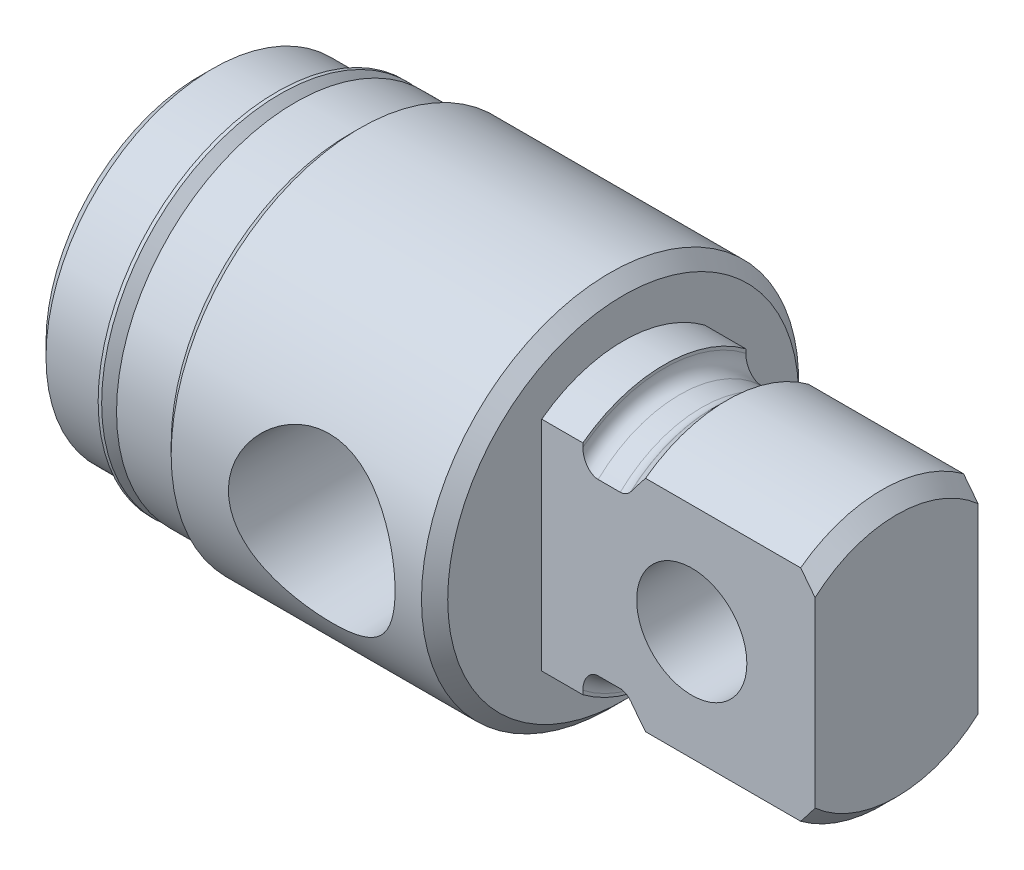
SolidWorks part; units mm, degrees
material "AISI 304"
ref_plane "Front Plane" through (0, 0, 0) normal (0, 0, 1) x (1, 0, 0)
ref_plane "Top Plane" through (0, 0, 0) normal (0, 1, 0) x (1, 0, 0)
ref_plane "Right Plane" through (0, 0, 0) normal (1, 0, 0) x (0, 0, -1)
ref_plane "Plane1" through (40.4876, 0, 0) normal (1, 0, 0) x (0, 0, -1)
sketch "Sketch1" plane through (0, 0, 0) normal (0, 0, 1) x (1, 0, 0)
  line L0 (0, 0) -> (0, 8.9091)
  line L1 (0, 8.9091) -> (0.762, 9.671)
  line L2 (0.762, 9.671) -> (4.0386, 9.671)
  line L3 (4.0386, 9.671) -> (4.8006, 8.9091)
  line L4 (4.8006, 8.9091) -> (5.5626, 8.9091)
  line L5 (5.5626, 8.9091) -> (5.5626, 10.3759)
  line L6 (5.5626, 10.3759) -> (8.7363, 10.3759)
  line L7 (8.7363, 10.3759) -> (9.3142, 10.9537)
  line L8 (9.3142, 10.9537) -> (23.8506, 10.9537)
  line L9 (23.8506, 10.9537) -> (24.6126, 10.1918)
  line L10 (24.6126, 10.1918) -> (24.6126, 0)
  line L11 (24.6126, 0) -> (0, 0)
  line L12 (24.6126, 0) -> (0, 0) construction
revolve "Revolve1" add sketch "Sketch1" angle 360 about L12 reverse direction yes
sketch "Sketch2" plane through (0, 0, 0) normal (0, 0, 1) x (1, 0, 0)
  line L0 (24.6126, 0) -> (24.6126, 7.9057)
  line L1 (24.6126, 7.9057) -> (27.0002, 7.9057)
  line L2 (27.0002, 7.9057) -> (27.0002, 7.7279)
  line L3 (27.8892, 6.8389) -> (29.1719, 6.8389)
  line L4 (29.7706, 7.0708) -> (29.8005, 7.098)
  line L5 (29.8005, 7.098) -> (30.64, 7.9375)
  line L6 (30.64, 7.9375) -> (39.6481, 7.9375)
  line L7 (39.6481, 7.9375) -> (40.4876, 7.098)
  line L8 (40.4876, 7.098) -> (40.4876, 0)
  line L9 (40.4876, 0) -> (24.6126, 0)
  line L10 (40.4876, 0) -> (24.6126, 0) construction
  arc A0 (27.0002, 7.7279) -> (27.8892, 6.8389) centre (27.8892, 7.7279) ccw
  arc A1 (29.1719, 6.8389) -> (29.7706, 7.0708) centre (29.1719, 7.7279) ccw
revolve "Revolve2" add sketch "Sketch2" angle 360 about L10 reverse direction yes
cosmetic thread "Cosmetic Thread1" parameters "D1"=10.6871, "D2"=14.1961
sketch "Sketch3" plane through (40.4876, 0, 0) normal (1, 0, 0) x (0, 0, -1)
  line L0 (-21.9075, -43.815) -> (21.9075, -43.815)
  line L1 (21.9075, -43.815) -> (21.9075, 43.815)
  line L2 (21.9075, 43.815) -> (-21.9075, 43.815)
  line L3 (-21.9075, 43.815) -> (-21.9075, -43.815)
  line L4 (-4.7307, -21.9075) -> (4.7307, -21.9075)
  line L5 (4.7307, -21.9075) -> (4.7307, 21.9075)
  line L6 (4.7307, 21.9075) -> (-4.7307, 21.9075)
  line L7 (-4.7307, 21.9075) -> (-4.7307, -21.9075)
extrude "Cut-Extrude1" cut sketch "Sketch3" against normal blind 15.875
ref_plane "Plane2" through (24.6126, 0, 0) normal (1, 0, 0) x (0, 0, -1)
hole_wizard "Hole1" positions "Sketch5" profile "Sketch4" legacy
sketch "Sketch5" plane through (0, 0, 0) normal (-1, 0, 0) x (0, 0, 1)
  point P0 (0, 0)
sketch "Sketch4" plane through (0, 0, 0) normal (0, 1, 0) x (0, 0, 1)
  line L0 (0, 0) -> (0, 25.8691)
  line L1 (0, 25.8691) -> (3.9624, 23.5814)
  line L2 (3.9624, 23.5814) -> (3.9624, 0)
  line L4 (3.9624, 0) -> (0, 0)
  line L6 (0, 25.8691) -> (-3.9624, 23.5814) construction
  line L7 (0, -4.2442) -> (0, 117.3081) construction
  dimension "Diameter" = 7.9248
  dimension "Depth" = 23.5814
  dimension "Drill Angle" = 120
ref_plane "Plane3" through (0, 0, 0) normal (0, 0.9998, 0.0175) x (1, 0, 0)
sketch "Sketch6" plane through (0, 0, 0) normal (0, 0.9998, 0.0175) x (1, 0, 0)
  line L0 (17.4752, 0) -> (22.0752, 0)
  line L1 (22.0752, 0) -> (22.0752, -3.2829)
  line L2 (22.0752, -3.2829) -> (22.3147, -10.9537)
  line L3 (22.3147, -10.9537) -> (17.4752, -10.9537)
  line L4 (17.4752, -10.9537) -> (17.4752, 0)
  line L5 (17.4752, -10.9537) -> (17.4752, 0) construction
revolve "Cut-Revolve1" cut sketch "Sketch6" angle 360 about L5 reverse direction yes
ref_plane "Plane4" through (17.4752, 0, 0) normal (1, 0, 0) x (0, 0, -1)
ref_plane "Plane5" through (4.8006, 0, 0) normal (1, 0, 0) x (0, 0, -1)
sketch "Sketch7" plane through (0, 0, 0) normal (0, 0, 1) x (1, 0, 0)
  line L0 (4.4955, 10.2917) -> (5.4401, 9.3472)
  line L1 (5.4401, 9.1676) -> (5.1816, 8.9091)
  line L2 (5.1816, 8.9091) -> (4.8006, 8.9091)
  line L3 (4.8006, 8.9091) -> (4.8006, 8.6551)
  line L4 (4.8006, 8.6551) -> (5.5626, 8.655)
  line L5 (5.5626, 8.655) -> (5.5626, 9.512)
  line L6 (5.5626, 9.512) -> (4.6987, 10.3759)
  line L7 (4.6987, 10.3759) -> (4.4955, 10.3759)
  line L8 (4.4955, 10.3759) -> (4.4955, 10.2917)
  line L9 (5.5626, 0) -> (4.8006, 0) construction
  arc A0 (5.4401, 9.3472) -> (5.4401, 9.1676) centre (5.3503, 9.2574) cw
revolve "Revolve3" add sketch "Sketch7" angle 360 about L9 reverse direction yes
ref_plane "Plane6" through (40.6146, 0, 0) normal (1, 0, 0) x (0, 0, -1)
sketch "Sketch8" plane through (0, 0, 0) normal (0, 0, 1) x (1, 0, 0)
  circle A0 centre (33.3248, 0) radius 3.2004
extrude "Cut-Extrude2" cut sketch "Sketch8" along normal blind 7.0961 and the other way blind 7.0961
ref_plane "Plane7" through (27.0002, 0, 0) normal (1, 0, 0) x (0, 0, -1)
ref_plane "Plane8" through (35.7124, 0, 0) normal (1, 0, 0) x (0, 0, -1)
ref_plane "Plane9" through (33.3248, 0, 0) normal (1, 0, 0) x (0, 0, -1)
ref_plane "Plane10" through (40.4876, 0, 0) normal (1, 0, 0) x (0, 0, -1)
ref_plane "Plane11" through (0, 0, 0) normal (0, 0, 1) x (1, 0, 0)
ref_plane "Plane12" through (27.0002, 0, 0) normal (1, 0, 0) x (0, 0, -1)
ref_plane "Plane13" through (0, 0, 0) normal (0, 1, 0) x (1, 0, 0)
ref_plane "Plane14" through (0, 2.032, 0) normal (0, 1, 0) x (1, 0, 0)
ref_plane "Plane15" through (24.6126, 0, 0) normal (1, 0, 0) x (0, 0, -1)
ref_plane "1 XY" through (27.0002, 0, 0) normal (1, 0, 0) x (0, 0, -1)
ref_plane "1 XZ" through (0, 0, 0) normal (0, -1, 0) x (-1, 0, 0)
ref_plane "1 YZ" through (0, 0, 0) normal (0, 0, -1) x (-1, 0, 0)
ref_axis "1 X" through (27.0002, 0, 80.9) along (0, 0, -1)
ref_axis "1 Y" through (27.0002, -50, 0) along (0, 1, 0)
ref_axis "1 Z" through (80.9, 0, 0) along (-1, 0, 0)
sketch3d "1"
  point P0 (27.0002, 0, 0)
ref_plane "c1 XY" through (0, 0, 0) normal (0, 0, 1) x (1, 0, 0)
ref_plane "c1 XZ" through (0, 7.9057, 0) normal (0, -1, 0) x (-1, 0, 0)
ref_plane "c1 YZ" through (24.6126, 0, 0) normal (1, 0, 0) x (0, 0, -1)
ref_axis "c1 X" through (-80.9, 7.9057, 0) along (1, 0, 0)
ref_axis "c1 Y" through (24.6126, -50, 0) along (0, 1, 0)
ref_axis "c1 Z" through (24.6126, 7.9057, 80.9) along (0, 0, -1)
sketch3d "c1"
  point P0 (24.6126, 7.9057, 0)
ref_plane "c2 XY" through (0, 0, 0) normal (0, 0, 1) x (1, 0, 0)
ref_plane "c2 XZ" through (0, -7.9057, 0) normal (0, -1, 0) x (-1, 0, 0)
ref_plane "c2 YZ" through (24.6126, 0, 0) normal (1, 0, 0) x (0, 0, -1)
ref_axis "c2 X" through (-80.9, -7.9057, 0) along (1, 0, 0)
ref_axis "c2 Y" through (24.6126, -50, 0) along (0, 1, 0)
ref_axis "c2 Z" through (24.6126, -7.9057, 80.9) along (0, 0, -1)
sketch3d "c2"
  point P0 (24.6126, -7.9057, 0)
ref_plane "cc1 XY" through (0, 0, 0) normal (0, 0, 1) x (1, 0, 0)
ref_plane "cc1 XZ" through (0, 0, 0) normal (0, -1, 0) x (-1, 0, 0)
ref_plane "cc1 YZ" through (24.6126, 0, 0) normal (1, 0, 0) x (0, 0, -1)
ref_axis "cc1 X" through (-80.9, 0, 0) along (1, 0, 0)
ref_axis "cc1 Y" through (24.6126, -50, 0) along (0, 1, 0)
ref_axis "cc1 Z" through (24.6126, 0, 80.9) along (0, 0, -1)
sketch3d "cc1"
  point P0 (24.6126, 0, 0)
ref_plane "cc2 XY" through (0, 0, 0) normal (0, 0, 1) x (1, 0, 0)
ref_plane "cc2 XZ" through (0, 0, 0) normal (0, -1, 0) x (-1, 0, 0)
ref_plane "cc2 YZ" through (27.0002, 0, 0) normal (1, 0, 0) x (0, 0, -1)
ref_axis "cc2 X" through (-80.9, 0, 0) along (1, 0, 0)
ref_axis "cc2 Y" through (27.0002, -50, 0) along (0, 1, 0)
ref_axis "cc2 Z" through (27.0002, 0, 80.9) along (0, 0, -1)
sketch3d "cc2"
  point P0 (27.0002, 0, 0)
ref_plane "lovra1 XY" through (35.7124, 0, 0) normal (1, 0, 0) x (0, 0, -1)
ref_plane "lovra1 XZ" through (0, 0, 0) normal (0, -1, 0) x (-1, 0, 0)
ref_plane "lovra1 YZ" through (0, 0, 0) normal (0, 0, -1) x (-1, 0, 0)
ref_axis "lovra1 X" through (35.7124, 0, 80.9) along (0, 0, -1)
ref_axis "lovra1 Y" through (35.7124, -50, 0) along (0, 1, 0)
ref_axis "lovra1 Z" through (80.9, 0, 0) along (-1, 0, 0)
sketch3d "lovra1"
  point P0 (35.7124, 0, 0)
ref_plane "lovra2 XY" through (35.7124, 0, 0) normal (1, 0, 0) x (0, 0, -1)
ref_plane "lovra2 XZ" through (0, 7.874, 0) normal (0, -1, 0) x (-1, 0, 0)
ref_plane "lovra2 YZ" through (0, 0, 0) normal (0, 0, -1) x (-1, 0, 0)
ref_axis "lovra2 X" through (35.7124, 7.874, 80.9) along (0, 0, -1)
ref_axis "lovra2 Y" through (35.7124, -50, 0) along (0, 1, 0)
ref_axis "lovra2 Z" through (80.9, 7.874, 0) along (-1, 0, 0)
sketch3d "lovra2"
  point P0 (35.7124, 7.874, 0)
ref_plane "lovra21 XY" through (0, 0, 0) normal (1, 0, 0) x (0, 0, -1)
ref_plane "lovra21 XZ" through (0, 0, 0) normal (0, -1, 0) x (-1, 0, 0)
ref_plane "lovra21 YZ" through (0, 0, 5.2705) normal (0, 0, -1) x (-1, 0, 0)
ref_axis "lovra21 X" through (0, 0, 80.9) along (0, 0, -1)
ref_axis "lovra21 Y" through (0, -50, 5.2705) along (0, 1, 0)
ref_axis "lovra21 Z" through (80.9, 0, 5.2705) along (-1, 0, 0)
sketch3d "lovra21"
  point P0 (0, 0, 5.2705)
ref_plane "lovra22 XY" through (0, 0, 0) normal (1, 0, 0) x (0, 0, -1)
ref_plane "lovra22 XZ" through (0, 0, 0) normal (0, -1, 0) x (-1, 0, 0)
ref_plane "lovra22 YZ" through (0, 0, -5.2705) normal (0, 0, -1) x (-1, 0, 0)
ref_axis "lovra22 X" through (0, 0, 80.9) along (0, 0, -1)
ref_axis "lovra22 Y" through (0, -50, -5.2705) along (0, 1, 0)
ref_axis "lovra22 Z" through (80.9, 0, -5.2705) along (-1, 0, 0)
sketch3d "lovra22"
  point P0 (0, 0, -5.2705)
ref_plane "lovra3 XY" through (35.7124, 0, 0) normal (1, 0, 0) x (0, 0, -1)
ref_plane "lovra3 XZ" through (0, -7.874, 0) normal (0, -1, 0) x (-1, 0, 0)
ref_plane "lovra3 YZ" through (0, 0, 0) normal (0, 0, -1) x (-1, 0, 0)
ref_axis "lovra3 X" through (35.7124, -7.874, 80.9) along (0, 0, -1)
ref_axis "lovra3 Y" through (35.7124, -50, 0) along (0, 1, 0)
ref_axis "lovra3 Z" through (80.9, -7.874, 0) along (-1, 0, 0)
sketch3d "lovra3"
  point P0 (35.7124, -7.874, 0)
ref_plane "olen XY" through (33.3248, 0, 0) normal (1, 0, 0) x (0, 0, -1)
ref_plane "olen XZ" through (0, 0, 0) normal (0, -1, 0) x (-1, 0, 0)
ref_plane "olen YZ" through (0, 0, 0) normal (0, 0, -1) x (-1, 0, 0)
ref_axis "olen X" through (33.3248, 0, 80.9) along (0, 0, -1)
ref_axis "olen Y" through (33.3248, -50, 0) along (0, 1, 0)
ref_axis "olen Z" through (80.9, 0, 0) along (-1, 0, 0)
sketch3d "olen"
  point P0 (33.3248, 0, 0)
ref_plane "p1 XY" through (40.4876, 0, 0) normal (1, 0, 0) x (0, 0, -1)
ref_plane "p1 XZ" through (0, 0, 0) normal (0, -1, 0) x (-1, 0, 0)
ref_plane "p1 YZ" through (0, 0, 4.7307) normal (0, 0, -1) x (-1, 0, 0)
ref_axis "p1 X" through (40.4876, 0, 80.9) along (0, 0, -1)
ref_axis "p1 Y" through (40.4876, -50, 4.7307) along (0, 1, 0)
ref_axis "p1 Z" through (80.9, 0, 4.7307) along (-1, 0, 0)
sketch3d "p1"
  point P0 (40.4876, 0, 4.7307)
ref_plane "p2 XY" through (40.4876, 0, 0) normal (1, 0, 0) x (0, 0, -1)
ref_plane "p2 XZ" through (0, 0, 0) normal (0, -1, 0) x (-1, 0, 0)
ref_plane "p2 YZ" through (0, 0, -4.7307) normal (0, 0, -1) x (-1, 0, 0)
ref_axis "p2 X" through (40.4876, 0, 80.9) along (0, 0, -1)
ref_axis "p2 Y" through (40.4876, -50, -4.7307) along (0, 1, 0)
ref_axis "p2 Z" through (80.9, 0, -4.7307) along (-1, 0, 0)
sketch3d "p2"
  point P0 (40.4876, 0, -4.7307)
ref_plane "port XY" through (0, 0, 0) normal (0, 0, 1) x (1, 0, 0)
ref_plane "port XZ" through (0, 0, 0) normal (0, -1, 0) x (-1, 0, 0)
ref_plane "port YZ" through (17.4752, 0, 0) normal (1, 0, 0) x (0, 0, -1)
ref_axis "port X" through (-80.9, 0, 0) along (1, 0, 0)
ref_axis "port Y" through (17.4752, -50, 0) along (0, 1, 0)
ref_axis "port Z" through (17.4752, 0, 80.9) along (0, 0, -1)
sketch3d "port"
  point P0 (17.4752, 0, 0)
ref_plane "port2 XY" through (40.4876, 0, 0) normal (1, 0, 0) x (0, 0, -1)
ref_plane "port2 XZ" through (0, 0, 0) normal (0, -1, 0) x (-1, 0, 0)
ref_plane "port2 YZ" through (0, 0, 0) normal (0, 0, -1) x (-1, 0, 0)
ref_axis "port2 X" through (40.4876, 0, 80.9) along (0, 0, -1)
ref_axis "port2 Y" through (40.4876, -50, 0) along (0, 1, 0)
ref_axis "port2 Z" through (80.9, 0, 0) along (-1, 0, 0)
sketch3d "port2"
  point P0 (40.4876, 0, 0)
ref_plane "thd1 XY" through (40.4876, 0, 0) normal (1, 0, 0) x (0, 0, -1)
ref_plane "thd1 XZ" through (0, 0, 0) normal (0, -1, 0) x (-1, 0, 0)
ref_plane "thd1 YZ" through (0, 0, 7.9375) normal (0, 0, -1) x (-1, 0, 0)
ref_axis "thd1 X" through (40.4876, 0, 80.9) along (0, 0, -1)
ref_axis "thd1 Y" through (40.4876, -50, 7.9375) along (0, 1, 0)
ref_axis "thd1 Z" through (80.9, 0, 7.9375) along (-1, 0, 0)
sketch3d "thd1"
  point P0 (40.4876, 0, 7.9375)
ref_plane "thd2 XY" through (40.4876, 0, 0) normal (1, 0, 0) x (0, 0, -1)
ref_plane "thd2 XZ" through (0, 0, 0) normal (0, -1, 0) x (-1, 0, 0)
ref_plane "thd2 YZ" through (0, 0, -7.9375) normal (0, 0, -1) x (-1, 0, 0)
ref_axis "thd2 X" through (40.4876, 0, 80.9) along (0, 0, -1)
ref_axis "thd2 Y" through (40.4876, -50, -7.9375) along (0, 1, 0)
ref_axis "thd2 Z" through (80.9, 0, -7.9375) along (-1, 0, 0)
sketch3d "thd2"
  point P0 (40.4876, 0, -7.9375)
ref_plane "to_mounting_bracket XY" through (24.6126, 0, 0) normal (1, 0, 0) x (0, 0, -1)
ref_plane "to_mounting_bracket XZ" through (0, 0, 0) normal (0, -1, 0) x (-1, 0, 0)
ref_plane "to_mounting_bracket YZ" through (0, 0, 0) normal (0, 0, -1) x (-1, 0, 0)
ref_axis "to_mounting_bracket X" through (24.6126, 0, 80.9) along (0, 0, -1)
ref_axis "to_mounting_bracket Y" through (24.6126, -50, 0) along (0, 1, 0)
ref_axis "to_mounting_bracket Z" through (80.9, 0, 0) along (-1, 0, 0)
sketch3d "to_mounting_bracket"
  point P0 (24.6126, 0, 0)
ref_plane "to_nut XY" through (27.0002, 0, 0) normal (1, 0, 0) x (0, 0, -1)
ref_plane "to_nut XZ" through (0, 0, 0) normal (0, -1, 0) x (-1, 0, 0)
ref_plane "to_nut YZ" through (0, 0, 0) normal (0, 0, -1) x (-1, 0, 0)
ref_axis "to_nut X" through (27.0002, 0, 80.9) along (0, 0, -1)
ref_axis "to_nut Y" through (27.0002, -50, 0) along (0, 1, 0)
ref_axis "to_nut Z" through (80.9, 0, 0) along (-1, 0, 0)
sketch3d "to_nut"
  point P0 (27.0002, 0, 0)
ref_plane "to_pin XY" through (0, 0, 0) normal (0, 0, 1) x (1, 0, 0)
ref_plane "to_pin XZ" through (0, 0, 0) normal (0, -1, 0) x (-1, 0, 0)
ref_plane "to_pin YZ" through (33.3248, 0, 0) normal (1, 0, 0) x (0, 0, -1)
ref_axis "to_pin X" through (-80.9, 0, 0) along (1, 0, 0)
ref_axis "to_pin Y" through (33.3248, -50, 0) along (0, 1, 0)
ref_axis "to_pin Z" through (33.3248, 0, 80.9) along (0, 0, -1)
sketch3d "to_pin"
  point P0 (33.3248, 0, 0)
ref_plane "to_screw XY" through (0, 2.032, 0) normal (0, 1, 0) x (1, 0, 0)
ref_plane "to_screw XZ" through (0, 0, -6.0452) normal (0, 0, 1) x (1, 0, 0)
ref_plane "to_screw YZ" through (17.4752, 0, 0) normal (1, 0, 0) x (0, 0, -1)
ref_axis "to_screw X" through (-80.9, 2.032, -6.0452) along (1, 0, 0)
ref_axis "to_screw Y" through (17.4752, 2.032, 50) along (0, 0, -1)
ref_axis "to_screw Z" through (17.4752, 50, -6.0452) along (0, -1, 0)
sketch3d "to_screw"
  point P0 (17.4752, 2.032, -6.0452)
ref_plane "to_tube XY" through (4.8006, 0, 0) normal (1, 0, 0) x (0, 0, -1)
ref_plane "to_tube XZ" through (0, 0, 0) normal (0, -1, 0) x (-1, 0, 0)
ref_plane "to_tube YZ" through (0, 0, 0) normal (0, 0, -1) x (-1, 0, 0)
ref_axis "to_tube X" through (4.8006, 0, 80.9) along (0, 0, -1)
ref_axis "to_tube Y" through (4.8006, -50, 0) along (0, 1, 0)
ref_axis "to_tube Z" through (80.9, 0, 0) along (-1, 0, 0)
sketch3d "to_tube"
  point P0 (4.8006, 0, 0)
